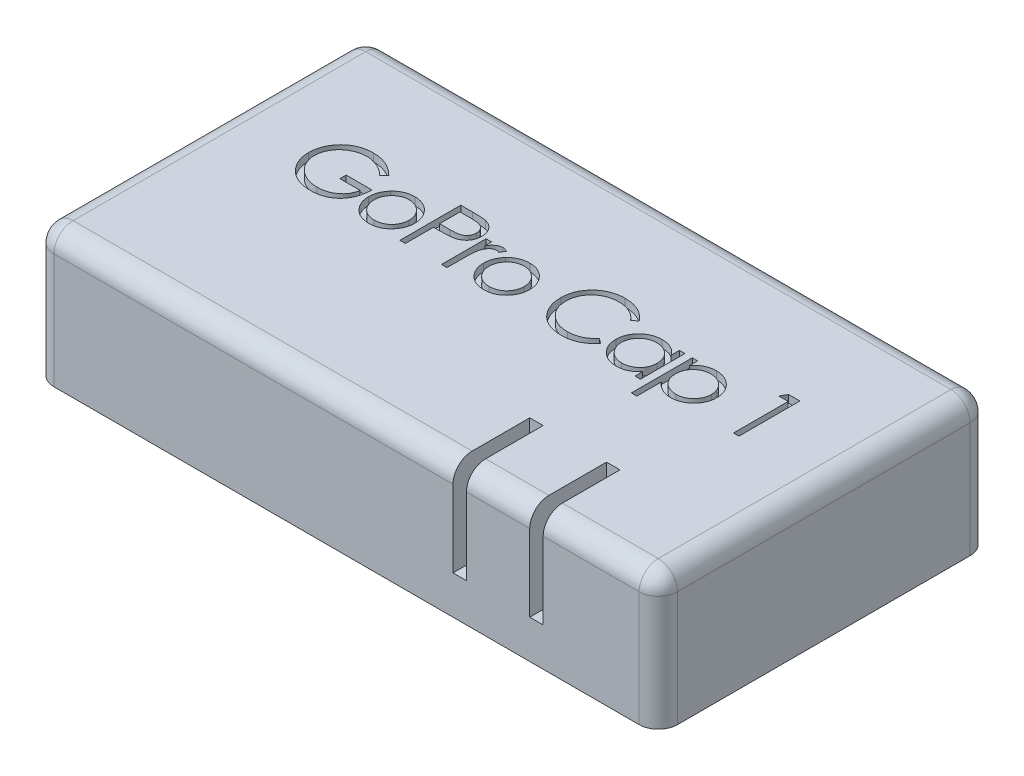
SolidWorks part; units mm, degrees
ref_plane "Front Plane" through (0, 0, 0) normal (0, 0, 1) x (1, 0, 0)
ref_plane "Top Plane" through (0, 0, 0) normal (0, 1, 0) x (1, 0, 0)
ref_plane "Right Plane" through (0, 0, 0) normal (1, 0, 0) x (0, 0, -1)
sketch "Sketch1" plane through (0, 0, 0) normal (0, 1, 0) x (1, 0, 0)
  line L0 (-16.25, 8.625) -> (16.25, 8.625)
  line L1 (-14.25, -6.625) -> (14.25, -6.625) construction
  line L2 (-14.25, -6.625) -> (-14.25, 6.625) construction
  line L3 (-14.25, 6.625) -> (14.25, 6.625) construction
  line L4 (14.25, -6.625) -> (14.25, 6.625) construction
  line L5 (-14.25, -6.625) -> (14.25, 6.625) construction
  line L6 (-14.25, 6.625) -> (14.25, -6.625) construction
  line L7 (16.25, -8.625) -> (16.25, 8.625)
  line L8 (-16.25, -8.625) -> (16.25, -8.625)
  line L9 (-16.25, -8.625) -> (-16.25, 8.625)
  point P0 (0, 0)
  dimension "D1" = 13.25
  dimension "D2" = 28.5
  dimension "D3" = 2
extrude "Boss-Extrude1" add sketch "Sketch1" along normal blind 7
sketch "Sketch2" plane through (0, 0, 0) normal (0, -1, 0) x (1, 0, 0)
  line L0 (-14.25, 6.625) -> (14.25, 6.625) construction
  line L1 (-14.25, 6.625) -> (-14.25, -6.625) construction
  line L2 (-14.25, -6.625) -> (14.25, -6.625) construction
  line L3 (14.25, 6.625) -> (14.25, -6.625) construction
  line L4 (-14.25, 6.625) -> (14.25, 6.625)
  line L5 (-14.25, 6.625) -> (-14.25, -6.625)
  line L6 (-14.25, -6.625) -> (14.25, -6.625)
  line L7 (14.25, 6.625) -> (14.25, -6.625)
extrude "Cut-Extrude1" cut sketch "Sketch2" against normal offset from surface (5 mm away) 2 up to face at (0, 7, 0)
fillet "Fillet1" radius 1 4 edges at (16.25, 7, 0) (0, 7, -8.625) (-16.25, 7, 0) (0, 7, 8.625)
fillet "Fillet2" radius 1 8 edges at (15.9571, 6.7071, 8.3321) (15.9571, 6.7071, -8.3321) (-15.9571, 6.7071, -8.3321) (-15.9571, 6.7071, 8.3321) (16.25, 3, 8.625) (16.25, 3, -8.625) (-16.25, 3, -8.625) (-16.25, 3, 8.625)
sketch "Sketch3" plane through (0, 5, 0) normal (0, -1, 0) x (1, 0, 0)
  line L0 (-14.25, 6.625) -> (14.25, 6.625) construction
  line L1 (9.55, 6.625) -> (10.25, 6.625)
  line L2 (9.55, 6.625) -> (9.55, 4.625)
  line L3 (9.55, 4.625) -> (10.25, 4.625)
  line L4 (10.25, 6.625) -> (10.25, 4.625)
  line L5 (14.25, 6.625) -> (14.25, -6.625) construction
  line L6 (5.55, 6.625) -> (6.25, 6.625)
  line L7 (5.55, 6.625) -> (5.55, 4.625)
  line L8 (5.55, 4.625) -> (6.25, 4.625)
  line L9 (6.25, 6.625) -> (6.25, 4.625)
  dimension "D1" = 0.7
  dimension "D2" = 2
  dimension "D3" = 4
  dimension "D4" = 0.7
  dimension "D5" = 2
  dimension "D6" = 8
extrude "Cut-Extrude2" cut sketch "Sketch3" against normal through all
sketch "Sketch4" plane through (0, 7, 0) normal (0, 1, 0) x (1, 0, 0)
  line L0 (-12.4302, 0) -> (12.4302, 0) construction
  text T0 "GoPro Cap 1" font "Century Gothic" height 3.175
  point P3 (0, 0)
extrude "Cut-Extrude3" cut sketch "Sketch4" against normal blind 0.4
sketch "Sketch5" plane through (0, 0, 8.625) normal (0, 0, 1) x (1, 0, 0)
  line L0 (9.55, 5) -> (10.25, 5) construction
  line L1 (9.55, 5) -> (10.25, 5)
  line L2 (9.55, 5) -> (9.55, 2.5)
  line L3 (9.55, 2.5) -> (10.25, 2.5)
  line L4 (10.25, 5) -> (10.25, 2.5)
  line L5 (5.55, 5) -> (6.25, 5)
  line L6 (5.55, 5) -> (5.55, 2.5)
  line L7 (5.55, 2.5) -> (6.25, 2.5)
  line L8 (6.25, 5) -> (6.25, 2.5)
  line L9 (5.55, 5) -> (6.25, 5) construction
  dimension "D1" = 0.7
  dimension "D2" = 2.5
  dimension "D3" = 0.7
  dimension "D4" = 2.5
extrude "Cut-Extrude4" [suppressed] cut sketch "Sketch5" against normal up to next
sketch "Sketch6" plane through (0, 7, 0) normal (0, 1, 0) x (1, 0, 0)
  line L0 (15.25, -8.625) -> (-15.25, -8.625) construction
  line L1 (10.25, -4.625) -> (9.55, -4.625)
  line L2 (10.25, -4.625) -> (10.25, -8.625)
  line L3 (10.25, -8.625) -> (9.55, -8.625)
  line L4 (9.55, -4.625) -> (9.55, -8.625)
  line L5 (9.55, -6.625) -> (9.55, -4.625) construction
  line L6 (5.55, -6.625) -> (5.55, -4.625) construction
  line L7 (6.25, -4.625) -> (5.55, -4.625)
  line L8 (6.25, -4.625) -> (6.25, -8.625)
  line L9 (6.25, -8.625) -> (5.55, -8.625)
  line L10 (5.55, -4.625) -> (5.55, -8.625)
extrude "Cut-Extrude6" cut sketch "Sketch6" against normal offset from surface (5 mm away) 3 up to face at (4.1375, 5, 3.75) offset beyond the face yes
